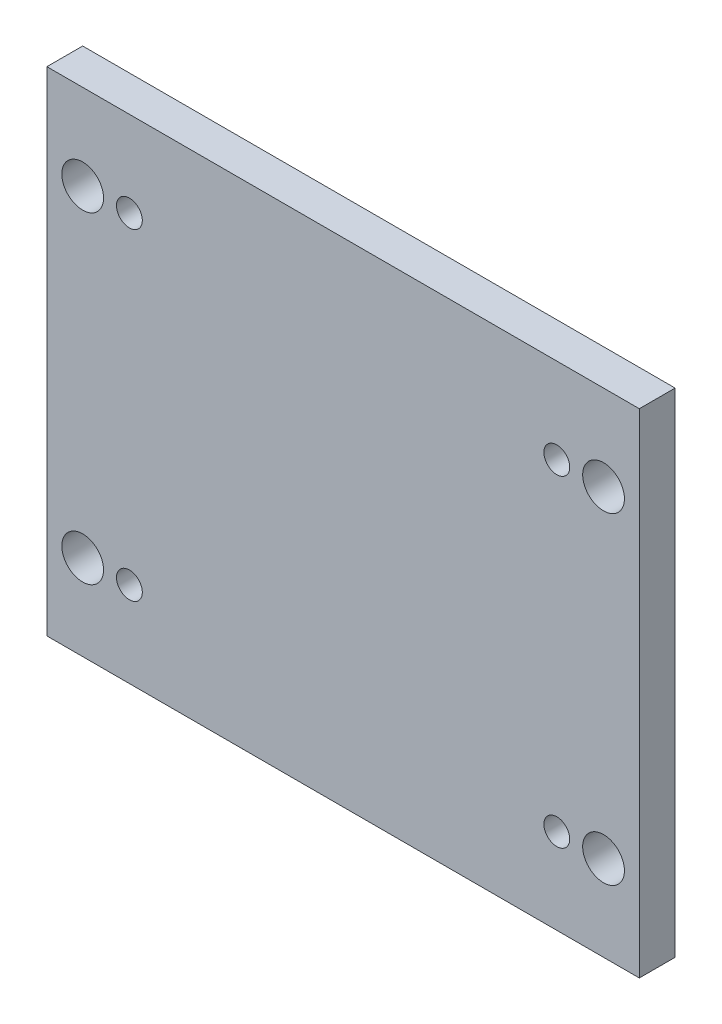
SolidWorks part; units mm, degrees
ref_plane "Płaszczyzna przednia" through (0, 0, 0) normal (0, 0, 1) x (1, 0, 0)
ref_plane "Płaszczyzna górna" through (0, 0, 0) normal (0, 1, 0) x (1, 0, 0)
ref_plane "Płaszczyzna prawa" through (0, 0, 0) normal (1, 0, 0) x (0, 0, -1)
sketch "Szkic1" plane through (0, 0, 0) normal (0, 0, 1) x (1, 0, 0)
  line L0 (-298, -248) -> (298, -248)
  line L1 (298, -248) -> (298, 248)
  line L2 (298, 248) -> (-298, 248)
  line L3 (-298, 248) -> (-298, -248)
extrude "Dodanie-wyciągnięcie1" add sketch "Szkic1" along normal blind 36
ref_plane "Płaszczyzna1" through (0, 0, 36) normal (0, 0, 1) x (1, 0, 0)
sketch "Szkic2" plane through (0, 0, 36) normal (0, 0, 1) x (1, 0, 0)
  circle A0 centre (262, 162) radius 21
extrude "Wytnij-wyciągnięcie1" cut sketch "Szkic2" against normal blind 36
sketch "Szkic3" plane through (0, 0, 36) normal (0, 0, 1) x (1, 0, 0)
  circle A0 centre (262, -162) radius 21
extrude "Wytnij-wyciągnięcie2" cut sketch "Szkic3" against normal blind 36
sketch "Szkic4" plane through (0, 0, 36) normal (0, 0, 1) x (1, 0, 0)
  circle A0 centre (-262, -162) radius 21
extrude "Wytnij-wyciągnięcie3" cut sketch "Szkic4" against normal blind 36
sketch "Szkic5" plane through (0, 0, 36) normal (0, 0, 1) x (1, 0, 0)
  circle A0 centre (-262, 162) radius 21
extrude "Wytnij-wyciągnięcie4" cut sketch "Szkic5" against normal blind 36
ref_plane "Płaszczyzna2" through (215, 0, 0) normal (1, 0, 0) x (0, 0, -1)
sketch "Szkic6" plane through (215, 0, 0) normal (1, 0, 0) x (0, 0, -1)
  line L0 (-15, 162) -> (-15, 171)
  line L1 (-15, 171) -> (0, 171)
  line L2 (0, 171) -> (0, 162)
  line L3 (0, 162) -> (-15, 162)
  line L4 (0, 162) -> (-15, 162) construction
revolve "Wycięcie-obrót1" cut sketch "Szkic6" angle 360 about L4 reverse direction yes
sketch "Szkic7" plane through (215, 0, 0) normal (1, 0, 0) x (0, 0, -1)
  line L0 (0, -162) -> (0, -171)
  line L1 (0, -171) -> (-15, -171)
  line L2 (-15, -171) -> (-15, -162)
  line L3 (-15, -162) -> (0, -162)
  line L4 (-15, -162) -> (0, -162) construction
revolve "Wycięcie-obrót2" cut sketch "Szkic7" angle 360 about L4 reverse direction yes
ref_plane "Płaszczyzna3" through (-215, 0, 0) normal (1, 0, 0) x (0, 0, -1)
sketch "Szkic8" plane through (-215, 0, 0) normal (1, 0, 0) x (0, 0, -1)
  line L0 (-15, 162) -> (-15, 171)
  line L1 (-15, 171) -> (0, 171)
  line L2 (0, 171) -> (0, 162)
  line L3 (0, 162) -> (-15, 162)
  line L4 (0, 162) -> (-15, 162) construction
revolve "Wycięcie-obrót3" cut sketch "Szkic8" angle 360 about L4 reverse direction yes
sketch "Szkic9" plane through (-215, 0, 0) normal (1, 0, 0) x (0, 0, -1)
  line L0 (0, -162) -> (0, -171)
  line L1 (0, -171) -> (-15, -171)
  line L2 (-15, -171) -> (-15, -162)
  line L3 (-15, -162) -> (0, -162)
  line L4 (-15, -162) -> (0, -162) construction
revolve "Wycięcie-obrót4" cut sketch "Szkic9" angle 360 about L4 reverse direction yes
sketch "Szkic10" plane through (215, 0, 0) normal (1, 0, 0) x (0, 0, -1)
  line L0 (-36, 162) -> (-36, 175)
  line L1 (-36, 175) -> (-15, 175)
  line L2 (-15, 175) -> (-15, 162)
  line L3 (-15, 162) -> (-36, 162)
  line L4 (-15, 162) -> (-36, 162) construction
revolve "Wycięcie-obrót5" cut sketch "Szkic10" angle 360 about L4 reverse direction yes
sketch "Szkic11" plane through (215, 0, 0) normal (1, 0, 0) x (0, 0, -1)
  line L0 (-15, -162) -> (-15, -175)
  line L1 (-15, -175) -> (-36, -175)
  line L2 (-36, -175) -> (-36, -162)
  line L3 (-36, -162) -> (-15, -162)
  line L4 (-36, -162) -> (-15, -162) construction
revolve "Wycięcie-obrót6" cut sketch "Szkic11" angle 360 about L4 reverse direction yes
sketch "Szkic12" plane through (-215, 0, 0) normal (1, 0, 0) x (0, 0, -1)
  line L0 (-15, -162) -> (-15, -175)
  line L1 (-15, -175) -> (-36, -175)
  line L2 (-36, -175) -> (-36, -162)
  line L3 (-36, -162) -> (-15, -162)
  line L4 (-36, -162) -> (-15, -162) construction
revolve "Wycięcie-obrót7" cut sketch "Szkic12" angle 360 about L4 reverse direction yes
sketch "Szkic13" plane through (-215, 0, 0) normal (1, 0, 0) x (0, 0, -1)
  line L0 (-36, 162) -> (-36, 175)
  line L1 (-36, 175) -> (-15, 175)
  line L2 (-15, 175) -> (-15, 162)
  line L3 (-15, 162) -> (-36, 162)
  line L4 (-15, 162) -> (-36, 162) construction
revolve "Wycięcie-obrót8" cut sketch "Szkic13" angle 360 about L4 reverse direction yes
ref_plane "Płaszczyzna4" through (0, 0, 15) normal (0, 0, 1) x (1, 0, 0)
ref_plane "IP1 XY" through (0, 0, 0) normal (0, 0, 1) x (1, 0, 0)
ref_plane "IP1 XZ" through (0, 0, 0) normal (0, -1, 0) x (-1, 0, 0)
ref_plane "IP1 YZ" through (0, 0, 0) normal (1, 0, 0) x (0, 0, -1)
ref_axis "IP1 X" through (-80.9, 0, 0) along (1, 0, 0)
ref_axis "IP1 Y" through (0, -50, 0) along (0, 1, 0)
ref_axis "IP1 Z" through (0, 0, 80.9) along (0, 0, -1)
sketch3d "IP1"
  point P0 (0, 0, 0)
ref_plane "IP2 XY" through (0, 0, 15) normal (0, 0, 1) x (1, 0, 0)
ref_plane "IP2 XZ" through (0, 162, 0) normal (0, -1, 0) x (-1, 0, 0)
ref_plane "IP2 YZ" through (-215, 0, 0) normal (1, 0, 0) x (0, 0, -1)
ref_axis "IP2 X" through (-80.9, 162, 15) along (1, 0, 0)
ref_axis "IP2 Y" through (-215, -50, 15) along (0, 1, 0)
ref_axis "IP2 Z" through (-215, 162, 80.9) along (0, 0, -1)
sketch3d "IP2"
  point P0 (-215, 162, 15)
ref_plane "IP3 XY" through (0, 0, 15) normal (0, 0, 1) x (1, 0, 0)
ref_plane "IP3 XZ" through (0, 162, 0) normal (0, -1, 0) x (-1, 0, 0)
ref_plane "IP3 YZ" through (215, 0, 0) normal (1, 0, 0) x (0, 0, -1)
ref_axis "IP3 X" through (-80.9, 162, 15) along (1, 0, 0)
ref_axis "IP3 Y" through (215, -50, 15) along (0, 1, 0)
ref_axis "IP3 Z" through (215, 162, 80.9) along (0, 0, -1)
sketch3d "IP3"
  point P0 (215, 162, 15)
ref_plane "IP4 XY" through (0, 0, 15) normal (0, 0, 1) x (1, 0, 0)
ref_plane "IP4 XZ" through (0, -162, 0) normal (0, -1, 0) x (-1, 0, 0)
ref_plane "IP4 YZ" through (215, 0, 0) normal (1, 0, 0) x (0, 0, -1)
ref_axis "IP4 X" through (-80.9, -162, 15) along (1, 0, 0)
ref_axis "IP4 Y" through (215, -50, 15) along (0, 1, 0)
ref_axis "IP4 Z" through (215, -162, 80.9) along (0, 0, -1)
sketch3d "IP4"
  point P0 (215, -162, 15)
ref_plane "IP5 XY" through (0, 0, 15) normal (0, 0, 1) x (1, 0, 0)
ref_plane "IP5 XZ" through (0, -162, 0) normal (0, -1, 0) x (-1, 0, 0)
ref_plane "IP5 YZ" through (-215, 0, 0) normal (1, 0, 0) x (0, 0, -1)
ref_axis "IP5 X" through (-80.9, -162, 15) along (1, 0, 0)
ref_axis "IP5 Y" through (-215, -50, 15) along (0, 1, 0)
ref_axis "IP5 Z" through (-215, -162, 80.9) along (0, 0, -1)
sketch3d "IP5"
  point P0 (-215, -162, 15)
